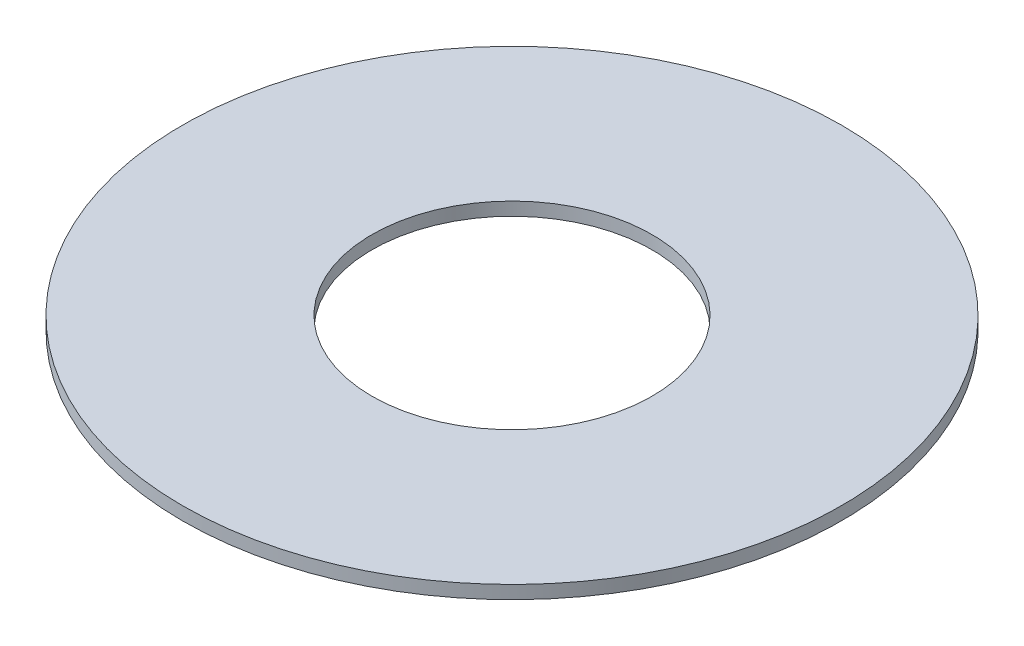
SolidWorks part; units mm, degrees
ref_plane "Front Plane" through (0, 0, 0) normal (0, 0, 1) x (1, 0, 0)
ref_plane "Top Plane" through (0, 0, 0) normal (0, 1, 0) x (1, 0, 0)
ref_plane "Right Plane" through (0, 0, 0) normal (1, 0, 0) x (0, 0, -1)
sketch "Sketch1" plane through (0, 0, 0) normal (0, 1, 0) x (1, 0, 0)
  circle A0 centre (0, 0) radius 100
  dimension "FLANGE_OD" = 200
extrude "Boss-Extrude1" add sketch "Sketch1" along normal blind 4
sketch "Sketch2" plane through (0, 0, 0) normal (0, 1, 0) x (1, 0, 0)
  circle A0 centre (0, 0) radius 42.5
  dimension "BORE_D" = 85
extrude "Cut-Extrude1" cut sketch "Sketch2" along normal through all
sketch "Sketch3" plane through (0, 4, 0) normal (0, 1, 0) x (1, 0, 0)
  circle A0 centre (0, 0) radius 24.7551 construction
  circle A1 centre (-24.7551, 0) radius 5.7435
  dimension "BOLT_D" = 11.4869
  dimension "BOLT_PCD" = 49.5102
extrude "Cut-Extrude2" cut sketch "Sketch3" against normal blind 3.2937 rebuild error yes
pattern_circular "CirPattern1" count 6 over 360 rebuild error yes
